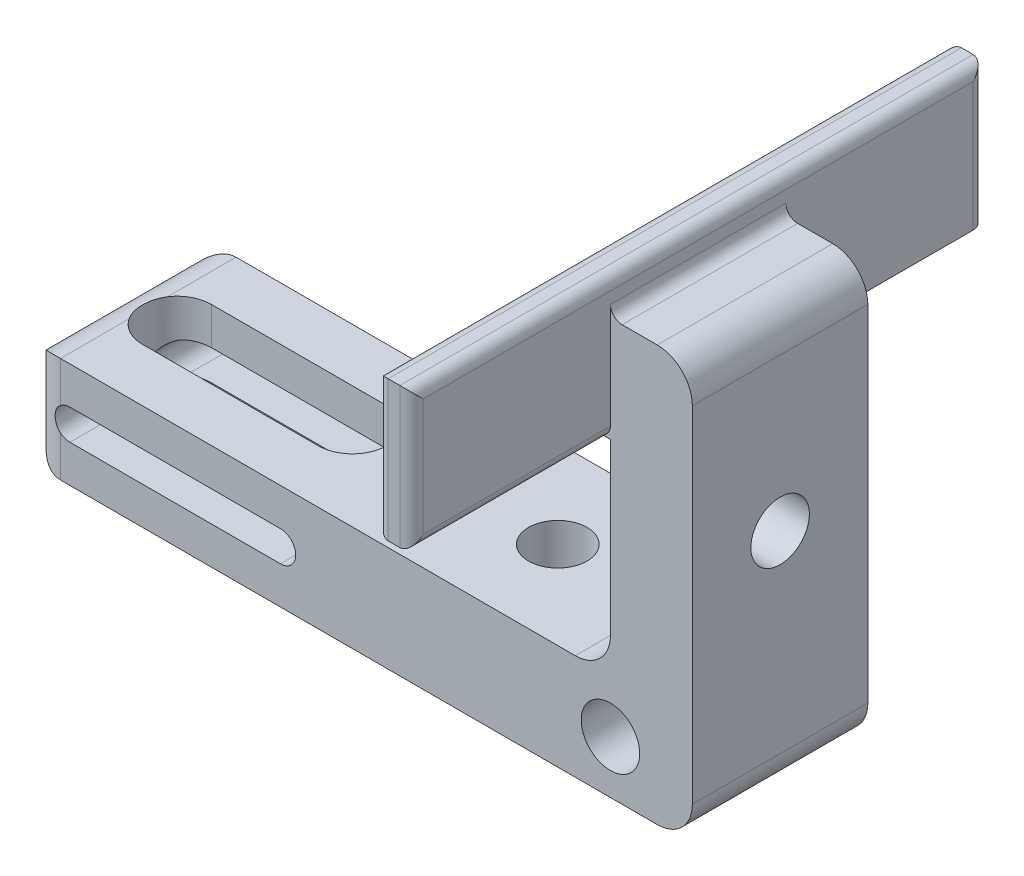
SolidWorks part; units mm, degrees
ref_plane "Front Plane" through (0, 0, 0) normal (0, 0, 1) x (1, 0, 0)
ref_plane "Top Plane" through (0, 0, 0) normal (0, 1, 0) x (1, 0, 0)
ref_plane "Right Plane" through (0, 0, 0) normal (1, 0, 0) x (0, 0, -1)
sketch "Sketch1" plane through (0, 0, 0) normal (0, 0, 1) x (1, 0, 0)
  line L0 (0, 0) -> (57, 0)
  line L1 (57, 0) -> (57, 35.5)
  line L2 (57, 35.5) -> (50, 35.5)
  line L3 (50, 35.5) -> (50, 9)
  line L4 (50, 9) -> (0, 9)
  line L5 (0, 9) -> (0, 0)
  dimension "D1" = 9
  dimension "D2" = 7
  dimension "D3" = 26.5
  dimension "D4" = 50
extrude "Boss-Extrude1" add sketch "Sketch1" against normal blind 15
sketch "Sketch2" plane through (0, 0, 0) normal (0, -1, 0) x (1, 0, 0)
  line L0 (0, -7.5) -> (57, -7.5) construction
  line L1 (0, -15) -> (0, 0) construction
  line L2 (57, -15) -> (57, 0) construction
  line L3 (5.45, -7.5) -> (20.45, -7.5) construction
  line L4 (5.45, -4.55) -> (20.45, -4.55)
  line L5 (5.45, -10.45) -> (20.45, -10.45)
  arc A0 (5.45, -4.55) -> (5.45, -10.45) centre (5.45, -7.5) ccw
  arc A1 (20.45, -10.45) -> (20.45, -4.55) centre (20.45, -7.5) ccw
  point P8 (12.95, -7.5)
  point P13 (2.5, -7.5)
  dimension "D1" = 5.9
  dimension "D2" = 2.5
  dimension "D3" = 15
extrude "Cut-Extrude1" cut sketch "Sketch2" against normal through all contours L5 A1 L4 A0
sketch "Sketch3" plane through (0, 0, 0) normal (0, 0, 1) x (1, 0, 0)
  line L0 (0, 4.5) -> (57, 4.5) construction
  line L1 (0, 9) -> (0, 0) construction
  line L2 (57, 0) -> (57, 35.5) construction
  line L3 (3.8, 4.5) -> (21.8, 4.5) construction
  line L4 (3.8, 5.8) -> (21.8, 5.8)
  line L5 (3.8, 3.2) -> (21.8, 3.2)
  arc A0 (3.8, 5.8) -> (3.8, 3.2) centre (3.8, 4.5) ccw
  arc A1 (21.8, 3.2) -> (21.8, 5.8) centre (21.8, 4.5) ccw
  point P8 (12.8, 4.5)
  point P13 (2.5, 4.5)
  dimension "D1" = 2.6
  dimension "D2" = 2.5
  dimension "D3" = 18
extrude "Cut-Extrude2" cut sketch "Sketch3" against normal through all
sketch "Sketch4" plane through (50, 0, 0) normal (-1, 0, 0) x (0, 0, 1)
  line L0 (-15, 35.5) -> (0, 35.5) construction
  line L1 (-32, 38.5) -> (17, 38.5)
  line L2 (-32, 38.5) -> (-32, 26.5)
  line L3 (-32, 26.5) -> (17, 26.5)
  line L4 (17, 38.5) -> (17, 26.5)
  line L5 (-15, 35.5) -> (-15, 9) construction
  line L6 (0, 35.5) -> (0, 9) construction
  dimension "D1" = 9
  dimension "D2" = 17
  dimension "D3" = 17
  dimension "D4" = 3
extrude "Boss-Extrude2" add sketch "Sketch4" along normal blind 3
sketch "Sketch5" plane through (0, 0, 0) normal (0, 0, 1) x (1, 0, 0)
  line L0 (50, 9) -> (50, 0) construction
  line L1 (0, 0) -> (57, 0) construction
  circle A0 centre (50, 4.5) radius 2.5
  dimension "D1" = 5
extrude "Cut-Extrude3" cut sketch "Sketch5" against normal through all
fillet "Fillet1" radius 3 2 edges at (50, 9, -7.5) (57, 0, -7.5)
fillet "Fillet2" radius 3 4 edges at (0, 0, -7.5) (0, 9, -7.5) (0, 4.5, -15) (0, 4.5, 0)
fillet "Fillet3" radius 1 8 edges at (50, 26.5, 8.5) (50, 32.5, -32) (50, 38.5, -7.5) (50, 32.5, 17) (47, 32.5, -32) (47, 32.5, 17) (47, 26.5, -7.5) (47, 38.5, -7.5)
fillet "Fillet4" radius 3 1 edges at (57, 35.5, -7.5)
fillet "Fillet5" radius 1 1 edges at (50, 35.5, -7.5)
sketch "Sketch6" plane through (50, 0, 0) normal (-1, 0, 0) x (0, 0, 1)
  circle A0 centre (-7.5, 19.4885) radius 2.5
  dimension "D1" = 5
extrude "Cut-Extrude4" cut sketch "Sketch6" against normal through all
sketch "Sketch7" plane through (0, 9, 0) normal (0, 1, 0) x (1, 0, 0)
  line L0 (47, 0) -> (47, 15) construction
  circle A0 centre (38, 7.5) radius 2.5
  dimension "D1" = 5
  dimension "D2" = 9
extrude "Cut-Extrude5" cut sketch "Sketch7" against normal through all
